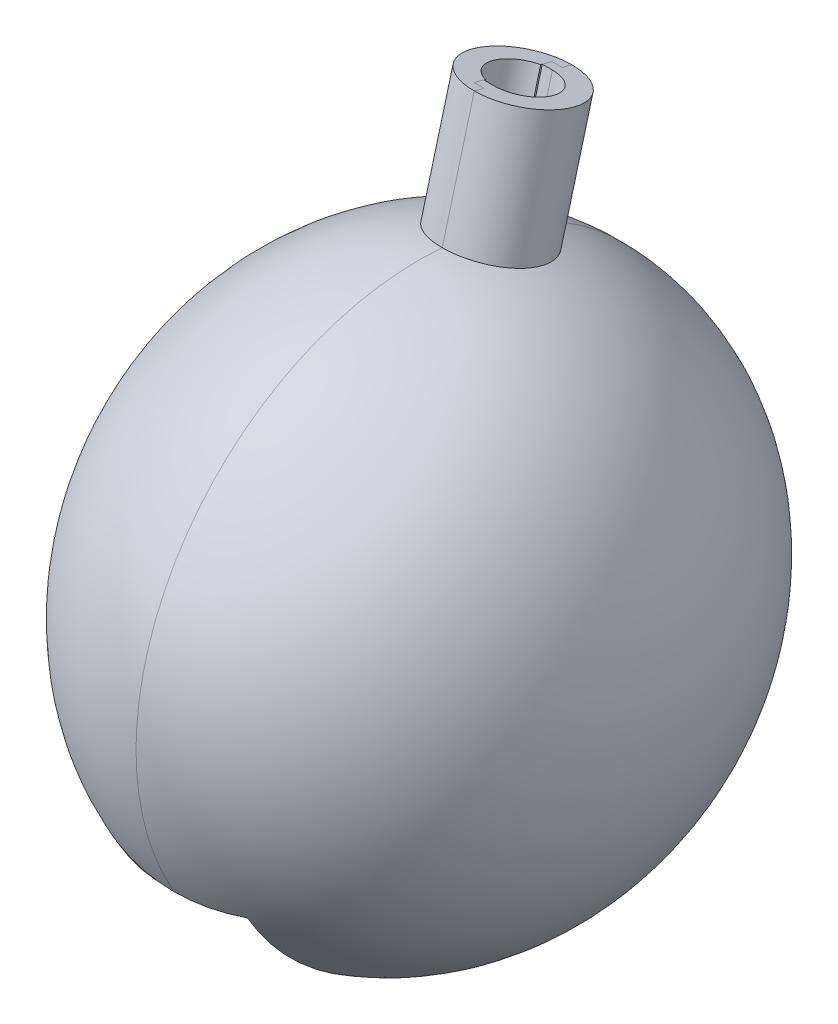
SolidWorks part; units mm, degrees
ref_plane "Front Plane" through (0, 0, 0) normal (0, 0, 1) x (1, 0, 0)
ref_plane "Top Plane" through (0, 0, 0) normal (0, 1, 0) x (1, 0, 0)
ref_plane "Right Plane" through (0, 0, 0) normal (1, 0, 0) x (0, 0, -1)
sketch "Sketch1" plane through (0, 0, 0) normal (0, 1, 0) x (1, 0, 0)
  line L0 (31.75, 0) -> (38.1, 0)
  line L2 (-31.75, 0) -> (31.75, 0) construction
  line L3 (0, 44.45) -> (0, 38.1)
  ellipse E0 centre (0, 0) end of major axis (0, 44.45) minor radius 38.1 (0, 44.45) -> (38.1, 0) cw
  ellipse E1 centre (0, 0) end of major axis (0, 38.1) minor radius 31.75 (0, 38.1) -> (31.75, 0) cw
  point P6 (0, 44.45)
  dimension "D4" = 6.35
  dimension "D1" = 6.35
  dimension "D3" = 44.45
revolve "Revolve1" add sketch "Sketch1" angle 210 about L2
sketch "Sketch2" plane through (0, 0, 0) normal (0, -1, 0) x (1, 0, 0)
  line L0 (0, 2.3286) -> (0, 50002.3286) construction
  line L1 (31.75, 0) -> (38.1, 0) construction
  line L2 (31.75, 0) -> (38.1, 0)
  line L14 (7.4422, 0) -> (50007.4422, 0) construction
  line L15 (10.16, -42.8404) -> (10.16, -41.2529)
  line L16 (10.16, -41.2529) -> (12.7, -41.2529)
  line L17 (12.7, -41.2529) -> (12.7, -37.9509)
  line L18 (12.7, -37.9509) -> (10.16, -37.9509)
  line L19 (10.16, -37.9509) -> (10.16, -36.0966)
  ellipse E0 centre (0, 0) end of major axis (0, -38.1) minor radius 31.75 (0, -38.1) -> (31.75, 0) ccw construction
  ellipse E1 centre (0, 0) end of major axis (0, -44.45) minor radius 38.1 (0, -44.45) -> (38.1, 0) ccw construction
  ellipse E2 centre (0, 0) end of major axis (0, -38.1) minor radius 31.75 (10.16, -36.0966) -> (31.75, 0) ccw
  ellipse E3 centre (0, 0) end of major axis (0, -44.45) minor radius 38.1 (10.16, -42.8404) -> (38.1, 0) ccw
  dimension "D1" = 3.302
  dimension "D2" = 1.5875
  dimension "D3" = 2.54
  dimension "D4" = 25.4
revolve "Revolve2" add sketch "Sketch2" angle 150 about L14 reverse direction yes
ref_axis "Axis2" through (41.91, 0, 0) along (-1, 0, 0)
ref_plane "Plane2" through (0, 0, 0) normal (0, 0.9659, -0.2588) x (-1, 0, 0)
sketch "Sketch5" plane through (0, 0, 0) normal (0, 0.9659, -0.2588) x (1, 0, 0)
  circle A0 centre (0, 0) radius 4.7625
  dimension "D1" = 9.525
extrude "Cut-Extrude1" cut sketch "Sketch5" along normal through all
ref_plane "Plane1" through (0, 36.5131, -9.7837) normal (0, 0.9659, -0.2588) x (1, 0, 0)
sketch "Sketch6" plane through (0, 36.5131, -9.7837) normal (0, 0.9659, -0.2588) x (1, 0, 0)
  line L0 (0, 4.7625) -> (0, 7.9375)
  line L1 (0, -4.7625) -> (0, -7.9375)
  arc A0 (0, -7.9375) -> (0, 7.9375) centre (0, 0) ccw
  arc A2 (0, -4.7625) -> (0, 4.7625) centre (0, 0) ccw
  arc A3 (0, -4.7625) -> (0, 4.7625) centre (0, 0) ccw construction
  dimension "D1" = 3.175
extrude "Boss-Extrude1" add sketch "Sketch6" along normal blind 25.4
ref_axis "Axis1" through (0, 59.3369, -15.8993) along (0, -0.9659, 0.2588)
ref_plane "Plane3" through (0, 0, 0) normal (0, -0.2588, -0.9659) x (-1, 0, 0)
sketch "Sketch10" plane through (0, 0, 0) normal (0, 0.2588, 0.9659) x (1, 0, 0)
  line L0 (7.9375, 43.4747) -> (7.9375, 63.2012) construction
  line L1 (7.9375, 60.0262) -> (6.35, 60.0262)
  line L2 (7.9375, 60.0262) -> (7.9375, 56.8512)
  line L3 (7.9375, 56.8512) -> (6.35, 56.8512)
  line L4 (6.35, 60.0262) -> (6.35, 56.8512)
  line L6 (7.9375, 63.2012) -> (0, 63.2012) construction
  dimension "D1" = 3.175
  dimension "D2" = 3.175
  dimension "D3" = 1.5875
revolve "Cut-Revolve3" [suppressed] cut sketch "Sketch10" angle 360 about axis through (0, 59.3369, -15.8993) along (0, -0.9659, 0.2588)
mirror "Mirror1" about plane through (0, 0, 0) normal (1, 0, 0) of bodies 105 111
sketch "Sketch14" plane through (0, 0, 0) normal (1, 0, 0) x (0, 0, -1)
  circle A0 centre (0, 0) radius 8.2804
  dimension "D1" = 16.5608
extrude "Cut-Extrude2" cut sketch "Sketch14" against normal blind 34.036
ref_plane "Plane4" through (25.4, 0, 0) normal (1, 0, 0) x (0, 0, -1)
sketch "Sketch15" plane through (25.4, 0, 0) normal (1, 0, 0) x (0, 0, -1)
  circle A0 centre (0, 0) radius 6.35
  dimension "D1" = 12.7
extrude "Boss-Extrude7" add sketch "Sketch15" along normal up to next
sketch "Sketch16" plane through (25.4, 0, 0) normal (-1, 0, 0) x (0, 0, 1)
  line L0 (-1.1176, 1.0022) -> (1.1176, 1.0022)
  arc A0 (-1.1176, 1.0022) -> (1.1176, 1.0022) centre (0, 0) ccw
  dimension "D1" = 3.0023
  dimension "D2" = 2.2352
extrude "Cut-Extrude3" cut sketch "Sketch16" against normal blind 9.525
sketch "Sketch17" plane through (0, 0, 0) normal (-1, 0, 0) x (0, 0, 1)
  line L0 (-38.1, 0) -> (-39.6875, 0)
  line L1 (-44.45, 0) -> (-38.1, 0) construction
  line L2 (-20.9579, 59.815) -> (-14.3839, 35.2805)
  line L3 (-11.7574, 62.2803) -> (-5.1834, 37.7458)
  line L4 (34.7465, 48.4449) -> (-54.3138, 24.5813) construction
  line L5 (-5.1834, 37.7458) -> (-11.7574, 62.2803) construction
  line L6 (-11.7574, 62.2803) -> (-10.224, 62.6911)
  line L7 (-11.7574, 62.2803) -> (-8.6906, 63.102) construction
  line L8 (-20.9579, 59.815) -> (-22.4913, 59.4041)
  line L9 (-24.0247, 58.9933) -> (-20.9579, 59.815) construction
  line L10 (32.9956, -19.05) -> (34.3704, -19.8437)
  line L11 (32.8665, -18.9755) -> (35.7261, -20.6265) construction
  line L12 (-22.4913, 59.4041) -> (-16.2732, 36.1978)
  line L13 (-10.224, 62.6911) -> (-4.0059, 39.4848)
  arc A0 (-38.1, 0) -> (-14.3839, 35.2805) centre (0, 0) cw
  arc A1 (-14.3839, 35.2805) -> (-38.1, 0) centre (0, 0) ccw construction
  arc A2 (-39.6875, 0) -> (-16.2732, 36.1978) centre (0, 0) cw
  arc A3 (-5.1834, 37.7458) -> (32.9956, -19.05) centre (0, 0) cw
  arc A4 (32.9956, -19.05) -> (-5.1834, 37.7458) centre (0, 0) ccw construction
  arc A5 (-4.0059, 39.4848) -> (34.3704, -19.8437) centre (0, 0) cw
  dimension "D1" = 1.5875
extrude "Boss-Extrude8" add sketch "Sketch17" along normal blind 1.5875
sketch "Sketch18" plane through (0, 0, 0) normal (1, 0, 0) x (0, 0, -1)
  line L0 (-38.4948, -22.225) -> (-32.9956, -19.05) construction
  line L1 (44.45, 0) -> (38.1, 0) construction
  line L2 (16.2732, 36.1978) -> (22.4913, 59.4041)
  line L3 (4.0059, 39.4848) -> (10.224, 62.6911)
  line L4 (11.7574, 62.2803) -> (8.6906, 63.102) construction
  line L5 (10.224, 62.6911) -> (22.4913, 59.4041)
  line L6 (39.6875, 0) -> (-34.3704, -19.8438)
  line L9 (20.9579, 59.815) -> (14.3839, 35.2805) construction
  line L10 (5.1834, 37.7458) -> (11.7574, 62.2803) construction
  line L11 (24.0247, 58.9933) -> (20.9579, 59.815) construction
  arc A0 (-34.3704, -19.8438) -> (4.0059, 39.4848) centre (0, 0) cw
  arc A1 (16.2732, 36.1978) -> (39.6875, 0) centre (0, 0) cw
  arc A2 (3.6526, 44.2997) -> (-38.4948, -22.225) centre (0, 0) ccw construction
  dimension "D1" = 1.5875
  dimension "D2" = 1.5875
  dimension "D3" = 1.5875
  dimension "D4" = 1.5875
extrude "Cut-Extrude5" cut sketch "Sketch18" against normal blind 1.5875
